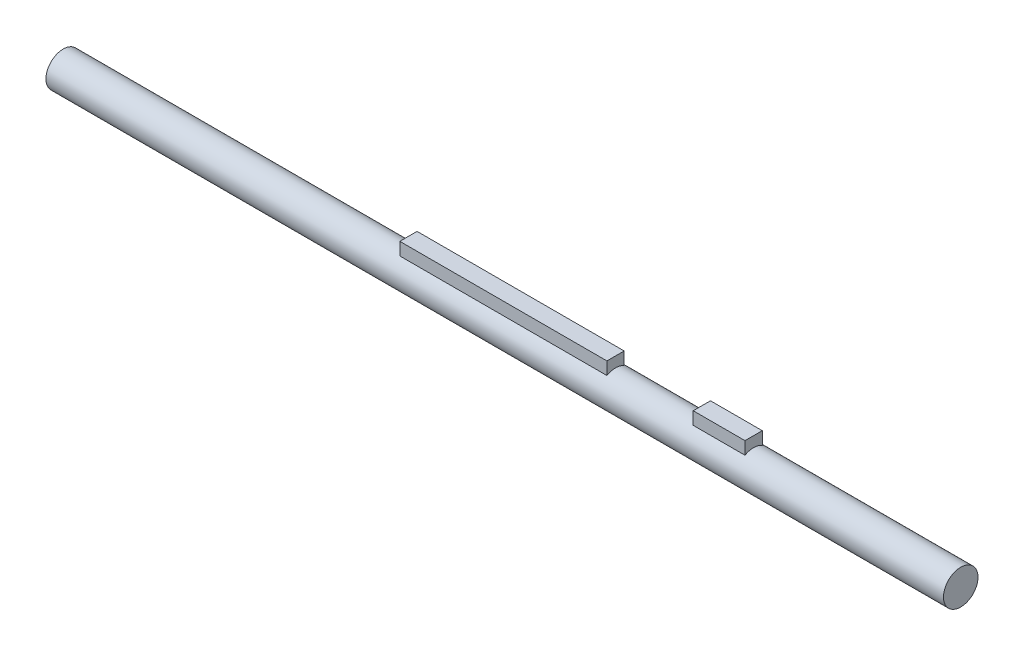
SolidWorks part; units mm, degrees
ref_plane "Front Plane" through (0, 0, 0) normal (0, 0, 1) x (1, 0, 0)
ref_plane "Top Plane" through (0, 0, 0) normal (0, 1, 0) x (1, 0, 0)
ref_plane "Right Plane" through (0, 0, 0) normal (1, 0, 0) x (0, 0, -1)
sketch "Sketch2" plane through (0, 0, 0) normal (1, 0, 0) x (0, 0, -1)
  circle A1 centre (0, 0) radius 5
  dimension "D1" = 10
extrude "Shaft" add sketch "Sketch2" along normal blind 130 and the other way blind 130
sketch "Sketch3" plane through (0, 0, 0) normal (1, 0, 0) x (0, 0, -1)
  line L1 (-2.5, 8) -> (2.5, 8)
  line L2 (-2.5, 8) -> (-2.5, 0)
  line L3 (-2.5, 0) -> (2.5, 0)
  line L4 (2.5, 8) -> (2.5, 0)
  line L5 (-2.5, 8) -> (2.5, 0) construction
  line L6 (-2.5, 0) -> (2.5, 8) construction
  point P0 (0, 4)
  dimension "D1" = 8
  dimension "D2" = 5
extrude "Shaft Key for Biceps" add sketch "Sketch3" along normal up to surface (130 mm away) and the other way blind 30 up to face at (130, 0, -5)
sketch "Sketch5" plane through (130, 0, 0) normal (1, 0, 0) x (0, 0, -1)
  line L0 (2.5, 4.3301) -> (2.5, 8) construction
  line L1 (-2.5, 4.3301) -> (-2.5, 8)
  line L2 (-2.5, 8) -> (2.5, 8)
  line L3 (2.5, 8) -> (2.5, 4.3301)
  arc A0 (-2.5, 4.3301) -> (2.5, 4.3301) centre (0, 0) cw
extrude "Cut-Extrude1" cut sketch "Sketch5" against normal blind 75
sketch "Sketch9" plane through (55, 0, 0) normal (1, 0, 0) x (0, 0, -1)
  line L0 (2.5, 4.3301) -> (2.5, 8)
  line L1 (2.5, 8) -> (-2.5, 8)
  line L2 (-2.5, 8) -> (-2.5, 4.3301)
  arc A0 (-2.5, 4.3301) -> (2.5, 4.3301) centre (0, 0) cw
  arc A1 (2.5, 4.3301) -> (-2.5, 4.3301) centre (0, 0) ccw construction
sketch "Sketch10" plane through (55, 0, 0) normal (1, 0, 0) x (0, 0, -1)
  line L0 (-2.5, 8) -> (2.5, 8)
  line L1 (2.5, 8) -> (2.5, 4.3301)
  line L2 (-2.5, 4.3301) -> (-2.5, 8)
  arc A0 (-2.5, 4.3301) -> (2.5, 4.3301) centre (0, 0) cw
  arc A1 (2.5, 4.3301) -> (-2.5, 4.3301) centre (0, 0) ccw construction
  arc M1 (-2.5, 4.3301) -> (2.5, 4.3301) centre (0, 0) cw
  line M2 (2.5, 4.3301) -> (2.5, 8)
  line M3 (2.5, 8) -> (-2.5, 8)
  line M4 (-2.5, 8) -> (-2.5, 4.3301)
extrude "Cut-Extrude2" cut sketch "Sketch9" against normal offset from surface (25 mm away) 60 up to face at (-30, 6.3325, 0)
extrude "Boss-Extrude1" add sketch "Sketch10" along normal blind 15 contours M4 M1 M2 M3 region at (55, 6.3855, 0)
